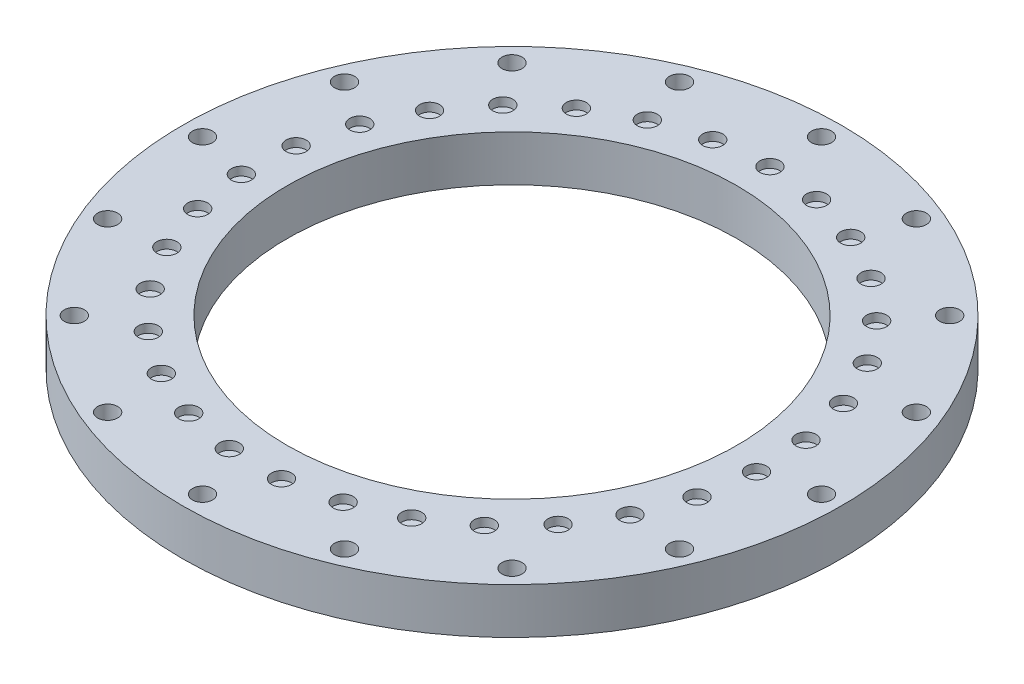
SolidWorks part; units mm, degrees
ref_plane "Front Plane" through (0, 0, 0) normal (0, 0, 1) x (1, 0, 0)
ref_plane "Top Plane" through (0, 0, 0) normal (0, 1, 0) x (1, 0, 0)
ref_plane "Right Plane" through (0, 0, 0) normal (1, 0, 0) x (0, 0, -1)
sketch "Sketch1" plane through (0, 0, 0) normal (0, 1, 0) x (1, 0, 0)
  circle A0 centre (0, 0) radius 57.5
  circle A1 centre (0, 0) radius 39.25
  dimension "D1" = 115
  dimension "D2" = 78.5
extrude "Boss-Extrude1" add sketch "Sketch1" along normal blind 8
sketch "Sketch2" plane through (0, 8, 0) normal (0, 1, 0) x (1, 0, 0)
  circle A0 centre (0, 0) radius 54 construction
  circle A1 centre (0, 54) radius 1.75
  circle A2 centre (20.6649, 49.8895) radius 1.75
  circle A3 centre (38.1838, 38.1838) radius 1.75
  circle A4 centre (49.8895, 20.6649) radius 1.75
  circle A5 centre (54, 0) radius 1.75
  circle A6 centre (49.8895, -20.6649) radius 1.75
  circle A7 centre (38.1838, -38.1838) radius 1.75
  circle A8 centre (20.6649, -49.8895) radius 1.75
  circle A9 centre (0, -54) radius 1.75
  circle A10 centre (-20.6649, -49.8895) radius 1.75
  circle A11 centre (-38.1838, -38.1838) radius 1.75
  circle A12 centre (-49.8895, -20.6649) radius 1.75
  circle A13 centre (-54, 0) radius 1.75
  circle A14 centre (-49.8895, 20.6649) radius 1.75
  circle A15 centre (-38.1838, 38.1838) radius 1.75
  circle A16 centre (-20.6649, 49.8895) radius 1.75
  point P37 (0, 0)
  dimension "D1" = 108
  dimension "D2" = 3.5
  dimension "D3" = 16
extrude "Cut-Extrude1" cut sketch "Sketch2" against normal blind 17
sketch "Sketch3" plane through (0, 8, 0) normal (0, 1, 0) x (1, 0, 0)
  circle A0 centre (0, 0) radius 45 construction
  circle A1 centre (0, 45) radius 1.75
  circle A2 centre (9.0584, 44.0788) radius 1.75
  circle A3 centre (17.746, 41.3531) radius 1.75
  circle A4 centre (25.7071, 36.9344) radius 1.75
  circle A5 centre (32.6157, 31.0035) radius 1.75
  circle A6 centre (38.189, 23.8034) radius 1.75
  circle A7 centre (42.1988, 15.6287) radius 1.75
  circle A8 centre (44.4811, 6.8142) radius 1.75
  circle A9 centre (44.9422, -2.2792) radius 1.75
  circle A10 centre (43.5635, -11.2794) radius 1.75
  circle A11 centre (40.4012, -19.8177) radius 1.75
  circle A12 centre (35.5849, -27.5448) radius 1.75
  circle A13 centre (29.3118, -34.1441) radius 1.75
  circle A14 centre (21.8386, -39.3456) radius 1.75
  circle A15 centre (13.4713, -42.9363) radius 1.75
  circle A16 centre (4.5526, -44.7691) radius 1.75
  circle A17 centre (-4.5526, -44.7691) radius 1.75
  circle A18 centre (-13.4713, -42.9363) radius 1.75
  circle A19 centre (-21.8386, -39.3456) radius 1.75
  circle A20 centre (-29.3118, -34.1441) radius 1.75
  circle A21 centre (-35.5849, -27.5448) radius 1.75
  circle A22 centre (-40.4012, -19.8177) radius 1.75
  circle A23 centre (-43.5635, -11.2794) radius 1.75
  circle A24 centre (-44.9422, -2.2792) radius 1.75
  circle A25 centre (-44.4811, 6.8142) radius 1.75
  circle A26 centre (-42.1988, 15.6287) radius 1.75
  circle A27 centre (-38.189, 23.8034) radius 1.75
  circle A28 centre (-32.6157, 31.0035) radius 1.75
  circle A29 centre (-25.7071, 36.9344) radius 1.75
  circle A30 centre (-17.746, 41.3531) radius 1.75
  circle A31 centre (-9.0584, 44.0788) radius 1.75
  point P67 (0, 0)
  dimension "D1" = 90
  dimension "D2" = 3.5
  dimension "D3" = 31
extrude "Cut-Extrude2" cut sketch "Sketch3" against normal blind 1.5
sketch "Sketch4" plane through (0, 0, 0) normal (0, -1, 0) x (1, 0, 0)
  circle A0 centre (0, 0) radius 50
  dimension "D1" = 100
sketch "Sketch5" plane through (0, 0, 0) normal (0, -1, 0) x (1, 0, 0)
  line L0 (0, 45) -> (0, 0) construction
  line L4 (0, 0) -> (26.5522, 0) construction
  circle A0 centre (0, 45) radius 2
  circle A1 centre (0, 0) radius 45 construction
  circle A2 centre (38.9711, -22.5) radius 2
  circle A3 centre (-38.9711, -22.5) radius 2
  point P11 (0, 0)
  dimension "D1" = 90
  dimension "D2" = 4
  dimension "D4" = 90
  dimension "D3" = 3
extrude "Cut-Extrude3" cut sketch "Sketch5" against normal blind 5
